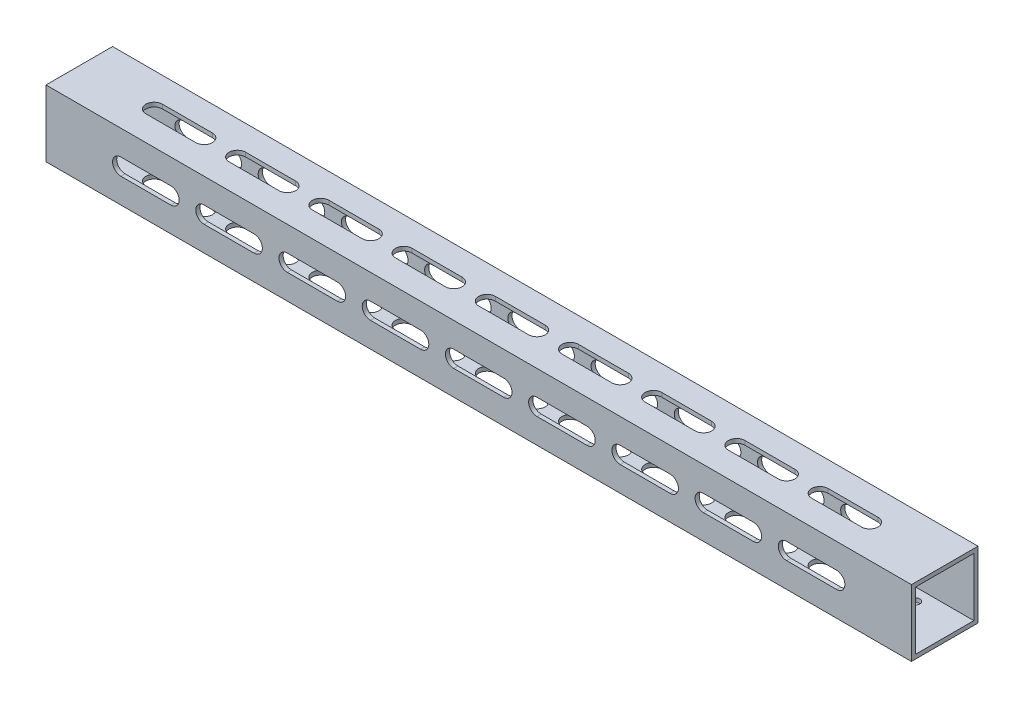
SolidWorks part; units mm, degrees
material "6061-T6 (SS)"
ref_plane "Front" through (0, 0, 0) normal (0, 0, 1) x (1, 0, 0)
ref_plane "Top" through (0, 0, 0) normal (0, 1, 0) x (1, 0, 0)
ref_plane "Right" through (0, 0, 0) normal (1, 0, 0) x (0, 0, -1)
sketch "Sketch1" plane through (0, 0, 0) normal (1, 0, 0) x (0, 0, -1)
  line L1 (-12.7, -12.7) -> (12.7, -12.7)
  line L2 (-12.7, -12.7) -> (-12.7, 12.7)
  line L3 (-12.7, 12.7) -> (12.7, 12.7)
  line L4 (12.7, -12.7) -> (12.7, 12.7)
  line L5 (-12.7, -12.7) -> (12.7, 12.7) construction
  line L6 (-12.7, 12.7) -> (12.7, -12.7) construction
  point P0 (0, 0)
  dimension "D1" = 25.4
extrude "Extrude-Thin1" add sketch "Sketch1" along normal up to surface (330.2 mm away) thin thin type one direction reverse wall 1.5875
sketch "Sketch4" plane through (0, -12.7, 0) normal (0, -1, 0) x (1, 0, 0)
  line L0 (0, 12.7) -> (0, -12.7) construction
  line L2 (17.4625, -6.35) -> (0, 0) construction
  line L3 (0, 0) -> (17.4625, 6.35) construction
  line L4 (165.1, -12.7) -> (165.1, 38.5816) construction
  line L5 (330.2, -12.7) -> (0, -12.7) construction
  point P0 (17.4625, -6.35)
  point P2 (26.9875, 6.35)
  point P7 (26.9875, -6.35)
  point P10 (17.4625, 6.35)
  point P22 (71.4375, -6.35)
  point P24 (61.9125, -6.35)
  point P26 (61.9125, 6.35)
  point P28 (71.4375, 6.35)
  point P37 (258.7625, 6.35)
  point P38 (268.2875, 6.35)
  point P39 (268.2875, -6.35)
  point P40 (258.7625, -6.35)
  point P41 (312.7375, 6.35)
  point P42 (303.2125, -6.35)
  point P43 (303.2125, 6.35)
  point P44 (312.7375, -6.35)
  dimension "D1" = 17.4625
  dimension "D2" = 9.525
  dimension "D3" = 12.7
  dimension "D4" = 44.45
  dimension "D5" = 9.525
hole_wizard "#30 (0.13) Diameter Hole1" positions "Sketch4" profile "Sketch3" hole size "#30" standard "ANSI Inch" end condition up to next
sketch "Sketch3" plane through (17.4625, -12.7, -6.35) normal (1, 0, 0) x (0, 0, -1)
  line L0 (0, 0) -> (0, 1.5875)
  line L1 (0, 1.5875) -> (1.651, 1.5875)
  line L2 (1.651, 1.5875) -> (1.651, 0)
  line L5 (1.651, 0) -> (0, 0)
  line L11 (0, -6.35) -> (0, 107.95) construction
  dimension "Thru Hole Dia." = 3.302
  dimension "Thru Hole Depth" = 1.5875
sketch "Sketch5" plane through (0, 12.7, 0) normal (0, 1, 0) x (1, 0, 0)
  line L0 (28.575, 0) -> (47.625, 0) construction
  line L1 (28.575, 3.175) -> (47.625, 3.175)
  line L2 (28.575, -3.175) -> (47.625, -3.175)
  line L3 (0, 12.7) -> (0, -12.7) construction
  line L4 (60.325, 0) -> (79.375, 0) construction
  line L5 (60.325, 3.175) -> (79.375, 3.175)
  line L6 (60.325, -3.175) -> (79.375, -3.175)
  line L7 (92.075, 0) -> (111.125, 0) construction
  line L8 (92.075, 3.175) -> (111.125, 3.175)
  line L9 (92.075, -3.175) -> (111.125, -3.175)
  line L10 (123.825, 0) -> (142.875, 0) construction
  line L11 (123.825, 3.175) -> (142.875, 3.175)
  line L12 (123.825, -3.175) -> (142.875, -3.175)
  line L13 (155.575, 0) -> (174.625, 0) construction
  line L14 (155.575, 3.175) -> (174.625, 3.175)
  line L15 (155.575, -3.175) -> (174.625, -3.175)
  line L16 (187.325, 0) -> (206.375, 0) construction
  line L17 (187.325, 3.175) -> (206.375, 3.175)
  line L18 (187.325, -3.175) -> (206.375, -3.175)
  line L19 (219.075, 0) -> (238.125, 0) construction
  line L20 (219.075, 3.175) -> (238.125, 3.175)
  line L21 (219.075, -3.175) -> (238.125, -3.175)
  line L22 (250.825, 0) -> (269.875, 0) construction
  line L23 (250.825, 3.175) -> (269.875, 3.175)
  line L24 (250.825, -3.175) -> (269.875, -3.175)
  line L25 (282.575, 0) -> (301.625, 0) construction
  line L26 (282.575, 3.175) -> (301.625, 3.175)
  line L27 (282.575, -3.175) -> (301.625, -3.175)
  arc A0 (28.575, 3.175) -> (28.575, -3.175) centre (28.575, 0) ccw
  arc A1 (47.625, -3.175) -> (47.625, 3.175) centre (47.625, 0) ccw
  arc A2 (60.325, 3.175) -> (60.325, -3.175) centre (60.325, 0) ccw
  arc A3 (79.375, -3.175) -> (79.375, 3.175) centre (79.375, 0) ccw
  arc A4 (92.075, 3.175) -> (92.075, -3.175) centre (92.075, 0) ccw
  arc A5 (111.125, -3.175) -> (111.125, 3.175) centre (111.125, 0) ccw
  arc A6 (123.825, 3.175) -> (123.825, -3.175) centre (123.825, 0) ccw
  arc A7 (142.875, -3.175) -> (142.875, 3.175) centre (142.875, 0) ccw
  arc A8 (155.575, 3.175) -> (155.575, -3.175) centre (155.575, 0) ccw
  arc A9 (174.625, -3.175) -> (174.625, 3.175) centre (174.625, 0) ccw
  arc A10 (187.325, 3.175) -> (187.325, -3.175) centre (187.325, 0) ccw
  arc A11 (206.375, -3.175) -> (206.375, 3.175) centre (206.375, 0) ccw
  arc A12 (219.075, 3.175) -> (219.075, -3.175) centre (219.075, 0) ccw
  arc A13 (238.125, -3.175) -> (238.125, 3.175) centre (238.125, 0) ccw
  arc A14 (250.825, 3.175) -> (250.825, -3.175) centre (250.825, 0) ccw
  arc A15 (269.875, -3.175) -> (269.875, 3.175) centre (269.875, 0) ccw
  arc A16 (282.575, 3.175) -> (282.575, -3.175) centre (282.575, 0) ccw
  arc A17 (301.625, -3.175) -> (301.625, 3.175) centre (301.625, 0) ccw
  point P2 (38.1, 0)
  point P13 (69.85, 0)
  point P20 (101.6, 0)
  point P27 (133.35, 0)
  point P34 (165.1, 0)
  point P41 (196.85, 0)
  point P48 (228.6, 0)
  point P55 (260.35, 0)
  point P62 (292.1, 0)
  dimension "D3" = 28.575
  dimension "D5" = 12.7
  dimension "D1" = 6.35
  dimension "D2" = 19.05
  dimension "D4" = 9
extrude "Cut-Extrude1" cut sketch "Sketch5" against normal through all
sketch "Sketch6" plane through (0, 0, 12.7) normal (0, 0, 1) x (1, 0, 0)
  line L0 (28.575, 0) -> (47.625, 0) construction
  line L1 (28.575, 3.175) -> (47.625, 3.175)
  line L2 (28.575, -3.175) -> (47.625, -3.175)
  line L3 (0, 12.7) -> (0, -12.7) construction
  line L4 (60.325, 0) -> (79.375, 0) construction
  line L5 (60.325, 3.175) -> (79.375, 3.175)
  line L6 (60.325, -3.175) -> (79.375, -3.175)
  line L7 (92.075, 0) -> (111.125, 0) construction
  line L8 (92.075, 3.175) -> (111.125, 3.175)
  line L9 (92.075, -3.175) -> (111.125, -3.175)
  line L10 (123.825, 0) -> (142.875, 0) construction
  line L11 (123.825, 3.175) -> (142.875, 3.175)
  line L12 (123.825, -3.175) -> (142.875, -3.175)
  line L13 (155.575, 0) -> (174.625, 0) construction
  line L14 (155.575, 3.175) -> (174.625, 3.175)
  line L15 (155.575, -3.175) -> (174.625, -3.175)
  line L16 (187.325, 0) -> (206.375, 0) construction
  line L17 (187.325, 3.175) -> (206.375, 3.175)
  line L18 (187.325, -3.175) -> (206.375, -3.175)
  line L19 (219.075, 0) -> (238.125, 0) construction
  line L20 (219.075, 3.175) -> (238.125, 3.175)
  line L21 (219.075, -3.175) -> (238.125, -3.175)
  line L22 (250.825, 0) -> (269.875, 0) construction
  line L23 (250.825, 3.175) -> (269.875, 3.175)
  line L24 (250.825, -3.175) -> (269.875, -3.175)
  line L25 (282.575, 0) -> (301.625, 0) construction
  line L26 (282.575, 3.175) -> (301.625, 3.175)
  line L27 (282.575, -3.175) -> (301.625, -3.175)
  arc A0 (28.575, 3.175) -> (28.575, -3.175) centre (28.575, 0) ccw
  arc A1 (47.625, -3.175) -> (47.625, 3.175) centre (47.625, 0) ccw
  arc A2 (60.325, 3.175) -> (60.325, -3.175) centre (60.325, 0) ccw
  arc A3 (79.375, -3.175) -> (79.375, 3.175) centre (79.375, 0) ccw
  arc A4 (92.075, 3.175) -> (92.075, -3.175) centre (92.075, 0) ccw
  arc A5 (111.125, -3.175) -> (111.125, 3.175) centre (111.125, 0) ccw
  arc A6 (123.825, 3.175) -> (123.825, -3.175) centre (123.825, 0) ccw
  arc A7 (142.875, -3.175) -> (142.875, 3.175) centre (142.875, 0) ccw
  arc A8 (155.575, 3.175) -> (155.575, -3.175) centre (155.575, 0) ccw
  arc A9 (174.625, -3.175) -> (174.625, 3.175) centre (174.625, 0) ccw
  arc A10 (187.325, 3.175) -> (187.325, -3.175) centre (187.325, 0) ccw
  arc A11 (206.375, -3.175) -> (206.375, 3.175) centre (206.375, 0) ccw
  arc A12 (219.075, 3.175) -> (219.075, -3.175) centre (219.075, 0) ccw
  arc A13 (238.125, -3.175) -> (238.125, 3.175) centre (238.125, 0) ccw
  arc A14 (250.825, 3.175) -> (250.825, -3.175) centre (250.825, 0) ccw
  arc A15 (269.875, -3.175) -> (269.875, 3.175) centre (269.875, 0) ccw
  arc A16 (282.575, 3.175) -> (282.575, -3.175) centre (282.575, 0) ccw
  arc A17 (301.625, -3.175) -> (301.625, 3.175) centre (301.625, 0) ccw
  point P3 (38.1, 0)
  point P13 (69.85, 0)
  point P20 (101.6, 0)
  point P27 (133.35, 0)
  point P34 (165.1, 0)
  point P41 (196.85, 0)
  point P48 (228.6, 0)
  point P55 (260.35, 0)
  point P62 (292.1, 0)
  dimension "D3" = 28.575
  dimension "D5" = 12.7
  dimension "D1" = 6.35
  dimension "D2" = 19.05
  dimension "D4" = 9
extrude "Cut-Extrude2" cut sketch "Sketch6" against normal through all
